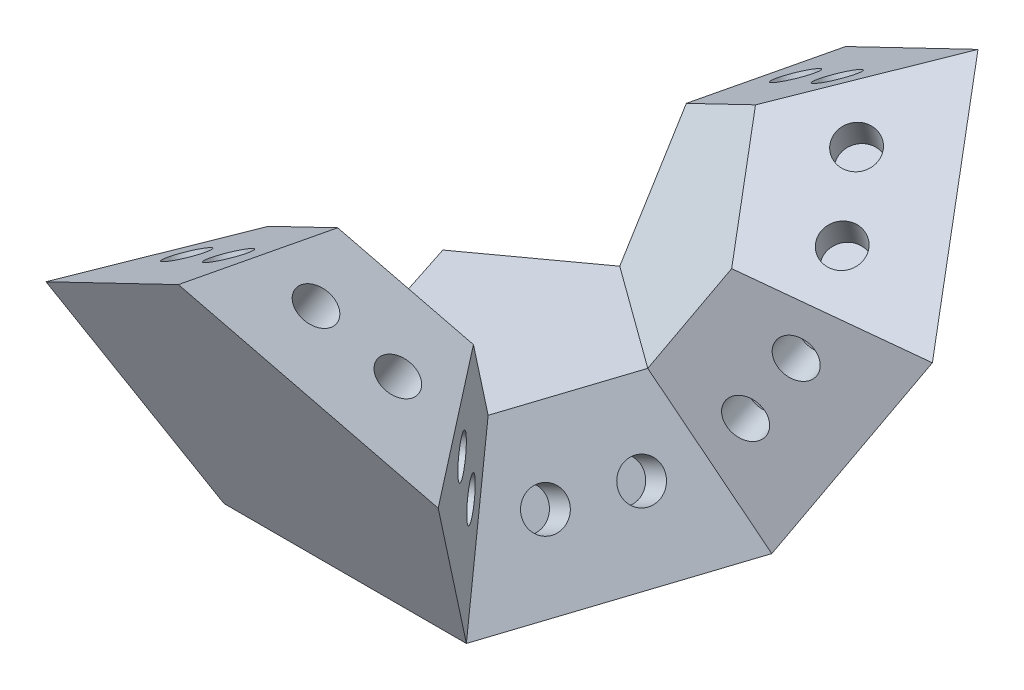
SolidWorks part; units mm, degrees
ref_plane "Front Plane" through (0, 0, 0) normal (0, 0, 1) x (1, 0, 0)
ref_plane "Top Plane" through (0, 0, 0) normal (0, 1, 0) x (1, 0, 0)
ref_plane "Right Plane" through (0, 0, 0) normal (1, 0, 0) x (0, 0, -1)
ref_axis "Axis1" through (0, 14.8487, 0) along (0, -1, 0)
sketch "Sketch1" plane through (0, 0, 0) normal (0, 1, 0) x (1, 0, 0)
  line L1 (0, 10.8033) -> (-10.2745, 3.3384)
  line L2 (-10.2745, 3.3384) -> (-6.35, -8.74)
  line L3 (-6.35, -8.74) -> (6.35, -8.74)
  line L4 (6.35, -8.74) -> (10.2745, 3.3384)
  line L5 (10.2745, 3.3384) -> (0, 10.8033)
  circle A0 centre (0, 0) radius 8.74 construction
  dimension "D1" = 12.7
extrude "Boss-Extrude1" add sketch "Sketch1" along normal blind 6.752 draft 31.717
sketch "Sketch3" plane through (0, 3.9087, 6.3243) normal (0, 0.5257, 0.8507) x (1, 0, 0)
  line L0 (-2, -0.6262) -> (2, -0.6262) construction
  line L1 (-6.35, -4.5949) -> (6.35, -4.5949) construction
  line L2 (-2, -4.5949) -> (-2, 3.3426) construction
  circle A0 centre (-2, -0.6262) radius 1
  circle A1 centre (2, -0.6262) radius 1
  point P4 (0, -0.6262)
  point P5 (-2, -0.6262)
  dimension "D1" = 2
  dimension "D2" = 4
  dimension "D3" = 7.9375
extrude "Cut-Extrude1" cut sketch "Sketch3" against normal blind 2
pattern_circular "CirPattern1" count 5 over 360 about axis through (0, 14.8487, 0) along (0, -1, 0) of "Cut-Extrude1"
mirror "Mirror1" [suppressed]
mirror "Mirror2" [suppressed]
mirror "Mirror3" about plane through (-6.35, 0, 8.74) normal (0, 0.5257, 0.8507) of "Boss-Extrude1", "CirPattern1", "Cut-Extrude1"
mirror "Mirror4" [suppressed]
mirror "Mirror5" about plane through (10.2745, 0, -3.3384) normal (0.5, 0.5257, -0.6882) of "Boss-Extrude1", "CirPattern1", "Cut-Extrude1"
equation "\"angle\"= arccos ( - sqr ( 5 ) / 5 )"
equation "\"theta\"= 90 - \"angle\" / 2"
equation "\"side\"=0.5"
equation "\"D1@Sketch1\"=\"side\""
equation "\"D3@Boss-Extrude1\"=\"theta\""
equation "\"D1@Boss-Extrude1\"=\"height\""
equation "\"face_height\"= .3125in"
equation "\"height\"= \"face_height\" * cos ( \"theta\" )"
equation "\"D3@Sketch3\"=\"face_height\""
